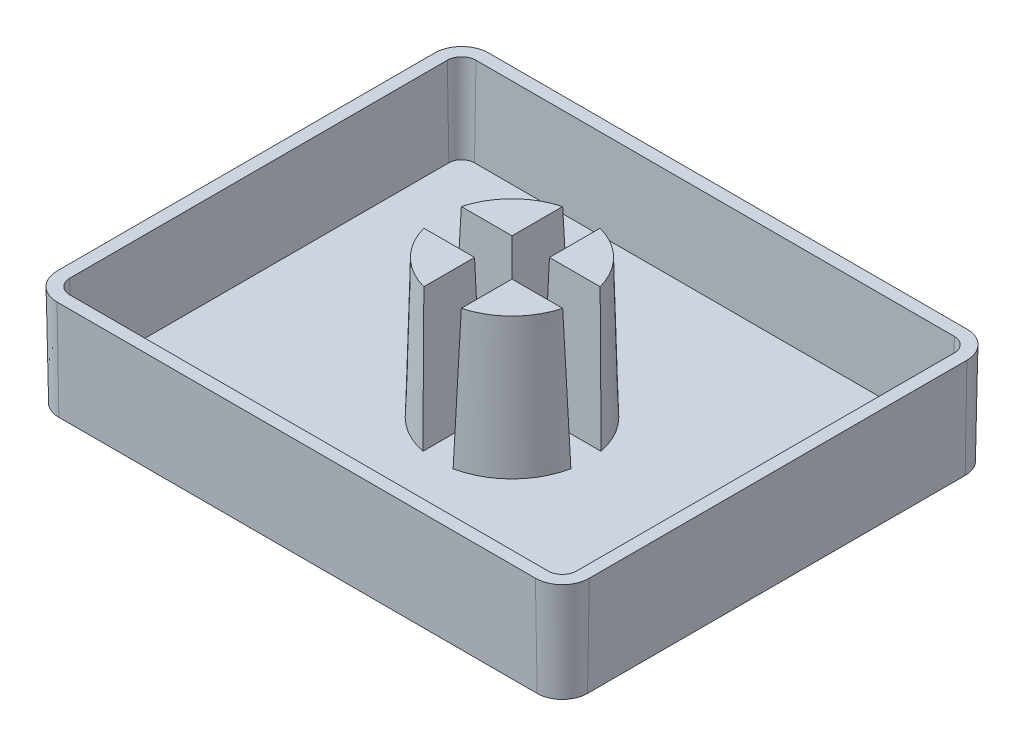
SolidWorks part; units mm, degrees
ref_plane "Front Plane" through (0, 0, 0) normal (0, 0, 1) x (1, 0, 0)
ref_plane "Top Plane" through (0, 0, 0) normal (0, 1, 0) x (1, 0, 0)
ref_plane "Right Plane" through (0, 0, 0) normal (1, 0, 0) x (0, 0, -1)
sketch "Sketch1" plane through (0, 0, 0) normal (0, 1, 0) x (1, 0, 0)
  line L1 (-9.5, -8.5) -> (9.5, -8.5)
  line L2 (-10.5, -7.5) -> (-10.5, 7.5)
  line L3 (-9.5, 8.5) -> (9.5, 8.5)
  line L4 (10.5, -7.5) -> (10.5, 7.5)
  line L5 (-10.5, -8.5) -> (10.5, 8.5) construction
  line L6 (-10.5, 8.5) -> (10.5, -8.5) construction
  arc A0 (-10.5, 7.5) -> (-9.5, 8.5) centre (-9.5, 7.5) cw
  arc A1 (10.5, 7.5) -> (9.5, 8.5) centre (9.5, 7.5) ccw
  arc A2 (10.5, -7.5) -> (9.5, -8.5) centre (9.5, -7.5) cw
  arc A3 (-9.5, -8.5) -> (-10.5, -7.5) centre (-9.5, -7.5) cw
  point P0 (0, 0)
  dimension "D3" = 1
  dimension "D1" = 21
  dimension "D2" = 17
extrude "Boss-Extrude1" add sketch "Sketch1" along normal blind 4 draft 1 draft outward yes
shell "Shell1" thickness 0.5 removed face at (0, 4, 0)
sketch "Sketch2" plane through (0, 0.5, 0) normal (0, 1, 0) x (1, 0, 0)
  line L0 (-0.6, 2.9394) -> (-0.6, 0.6)
  line L1 (-2.9394, 0.6) -> (-0.6, 0.6)
  line L2 (0, -2.2) -> (0, 2.2) construction
  line L3 (-2.2, 0) -> (2.2, 0) construction
  line L4 (-2.9394, -0.6) -> (-0.6, -0.6)
  line L5 (0.6, 2.9394) -> (0.6, 0.6)
  line L6 (0.6, 0.6) -> (2.9394, 0.6)
  line L7 (0.6, -0.6) -> (2.9394, -0.6)
  line L8 (0.6, -0.6) -> (0.6, -2.9394)
  line L9 (-0.6, -0.6) -> (-0.6, -2.9394)
  arc A0 (-0.6, 2.9394) -> (-2.9394, 0.6) centre (0, 0) ccw
  arc A1 (-2.9394, -0.6) -> (-0.6, -2.9394) centre (0, 0) ccw
  arc A2 (2.9394, 0.6) -> (0.6, 2.9394) centre (0, 0) ccw
  arc A3 (0.6, -2.9394) -> (2.9394, -0.6) centre (0, 0) ccw
  dimension "D1" = 0.6
  dimension "D2" = 0.6
extrude "Boss-Extrude2" add sketch "Sketch2" along normal blind 5.5 draft 1.5
